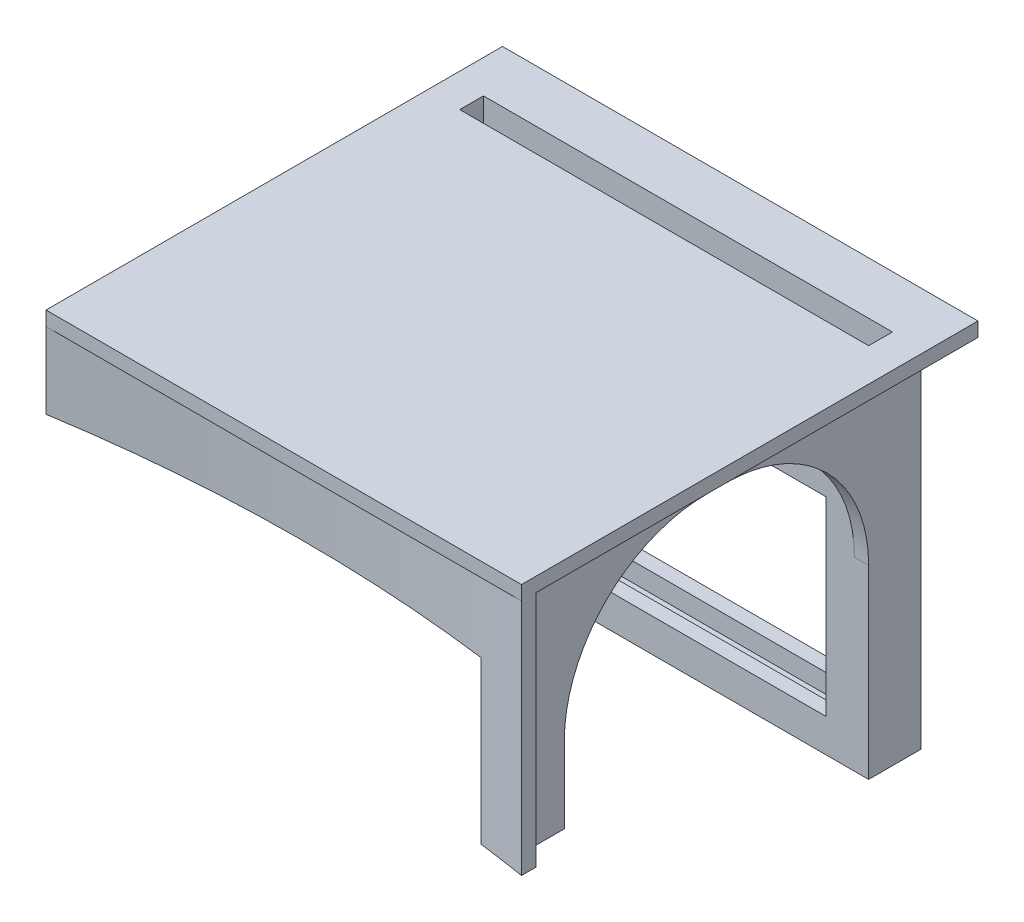
SolidWorks part; units mm, degrees
ref_plane "前视基准面" through (0, 0, 0) normal (0, 0, 1) x (1, 0, 0)
ref_plane "上视基准面" through (0, 0, 0) normal (0, 1, 0) x (1, 0, 0)
ref_plane "右视基准面" through (0, 0, 0) normal (1, 0, 0) x (0, 0, -1)
sketch "草图1" plane through (0, 0, 0) normal (0, 1, 0) x (1, 0, 0)
  line L0 (25, 0) -> (25, 48) construction
  line L1 (0, 0) -> (50, 0)
  line L2 (0, 0) -> (0, 48)
  line L3 (0, 48) -> (50, 48)
  line L4 (50, 0) -> (50, 48)
  line L5 (3.5, 42.5) -> (46.5, 42.5)
  line L6 (3.5, 42.5) -> (3.5, 40)
  line L7 (3.5, 40) -> (46.5, 40)
  line L8 (46.5, 42.5) -> (46.5, 40)
  point P11 (25, 42.5)
  point P12 (0, 0)
  dimension "D1" = 50
  dimension "D2" = 43
  dimension "D3" = 2.5
  dimension "D4" = 40
  dimension "D5" = 48
extrude "凸台-拉伸1" add sketch "草图1" along normal blind 1.5
sketch "草图2" plane through (0, 0, 0) normal (0, -1, 0) x (1, 0, 0)
  line L0 (2, -44) -> (2, -38.5)
  line L1 (3.5, -42.5) -> (46.5, -42.5)
  line L2 (3.5, -42.5) -> (3.5, -40)
  line L3 (3.5, -40) -> (46.5, -40)
  line L4 (46.5, -42.5) -> (46.5, -40)
  line L5 (2, -38.5) -> (48, -38.5)
  line L6 (48, -44) -> (48, -38.5)
  line L7 (2, -44) -> (48, -44)
  dimension "D1" = 1.5
extrude "凸台-拉伸2" add sketch "草图2" along normal blind 35
sketch "草图3" plane through (0, -35, 0) normal (0, -1, 0) x (1, 0, 0)
  line L1 (48, -38.5) -> (2, -38.5)
  line L2 (48, -38.5) -> (48, -44)
  line L3 (48, -44) -> (2, -44)
  line L4 (2, -38.5) -> (2, -44)
extrude "凸台-拉伸3" add sketch "草图3" along normal blind 1.5
sketch "草图4" plane through (0, 0, -44) normal (0, 0, -1) x (-1, 0, 0)
  line L0 (-25, -36.5) -> (-25, 8.4577) construction
  line L1 (-2, -36.5) -> (-48, -36.5) construction
  line L2 (-6.5, -33) -> (-43.5, -33)
  line L3 (-43.5, -33) -> (-43.5, -13)
  line L4 (-43.5, -13) -> (-6.5, -13)
  line L5 (-6.5, -33) -> (-6.5, -13)
  point P9 (-25, -13)
  point P10 (-25, -33)
  dimension "D1" = 3.5
  dimension "D2" = 37
  dimension "D3" = 20
extrude "切除-拉伸1" cut sketch "草图4" against normal blind 5.5
sketch "草图5" plane through (0, 0, 0) normal (0, -1, 0) x (1, 0, 0)
  line L0 (25, 0) -> (25, 57.502) construction
  line L1 (0, 0) -> (50, 0) construction
  line L2 (50, 0) -> (50, -1.5)
  line L3 (50, 0) -> (50, -48) construction
  line L4 (0, 0) -> (0, -1.5)
  line L5 (0, -48) -> (0, 0) construction
  line L6 (25, -2) -> (-4.7424, -2) construction
  arc A0 (0, 0) -> (50, 0) centre (25, 155.25) ccw
  arc A1 (0, -1.5) -> (50, -1.5) centre (25, 155.25) ccw
  dimension "D1" = 2
  dimension "D2" = 1.5
extrude "凸台-拉伸4" add sketch "草图5" along normal blind 25
sketch "草图6" plane through (48, 0, 0) normal (1, 0, 0) x (0, 0, -1)
  line L0 (38.5, -36.5) -> (38.5, 0) construction
  line L1 (44, 0) -> (1.5, 0)
  line L2 (44, 0) -> (44, -25)
  line L3 (44, -25) -> (38.5, -25)
  line L4 (1.5, 0) -> (1.5, -25)
  line L6 (6.5, -25) -> (6.5, -17)
  line L7 (21.5, -2) -> (23.5, -2)
  line L8 (38.5, -25) -> (38.5, -17)
  line L9 (6.5, -25) -> (1.5, -25)
  arc A0 (23.5, -2) -> (38.5, -17) centre (23.5, -17) cw
  arc A1 (6.5, -17) -> (21.5, -2) centre (21.5, -17) cw
  dimension "D1" = 15
  dimension "D2" = 5
  dimension "D3" = 2
extrude "凸台-拉伸5" add sketch "草图6" against normal blind 1.5
sketch "草图7" plane through (0, 0, 0) normal (0, 0, 1) x (1, 0, 0)
  line L0 (0, -25) -> (0, 0) construction
  line L1 (0, -8) -> (45, -8)
  line L2 (0, -8) -> (0, -25)
  line L3 (0, -25) -> (45, -25)
  line L4 (45, -8) -> (45, -25)
  line L5 (0, -25) -> (50, -25) construction
  line L6 (0, 0) -> (50, 0) construction
  line L7 (50, -25) -> (50, 0) construction
  dimension "D1" = 8
  dimension "D2" = 5
extrude "切除-拉伸2" cut sketch "草图7" against normal up to next
